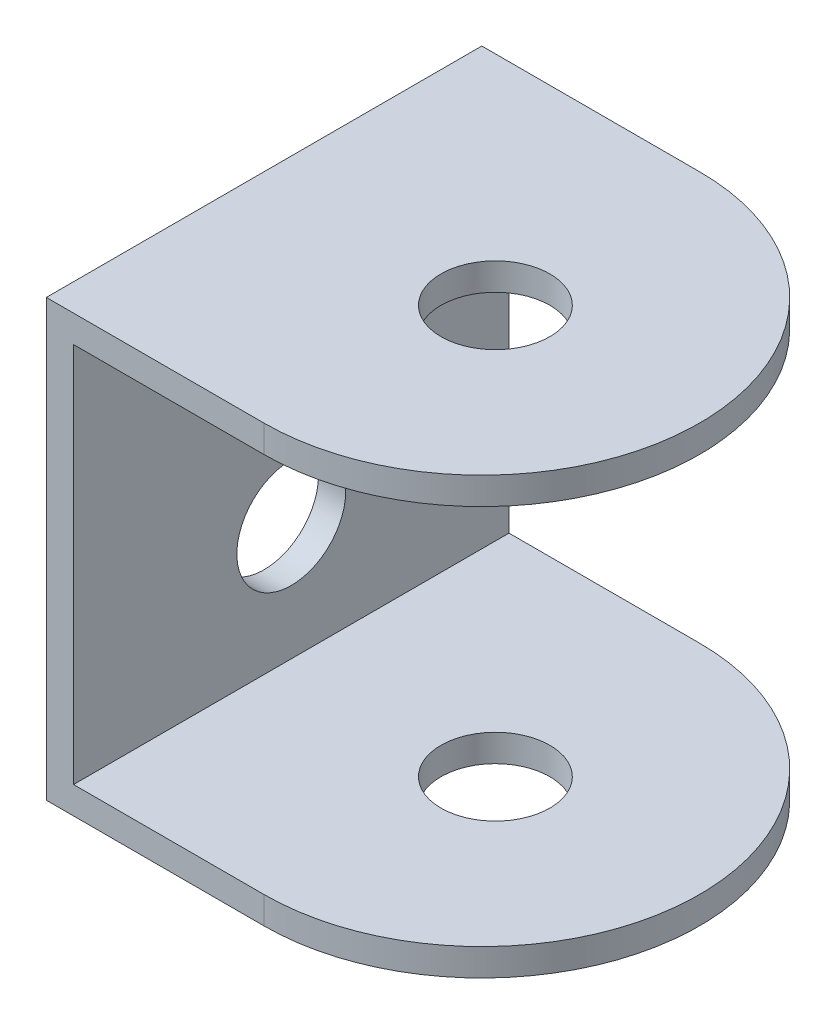
SolidWorks part; units mm, degrees
ref_plane "Front Plane" through (0, 0, 0) normal (0, 0, 1) x (1, 0, 0)
ref_plane "Top Plane" through (0, 0, 0) normal (0, 1, 0) x (1, 0, 0)
ref_plane "Right Plane" through (0, 0, 0) normal (1, 0, 0) x (0, 0, -1)
sketch "Sketch1" plane through (0, 0, 0) normal (0, 0, 1) x (1, 0, 0)
  line L1 (0, 0) -> (25.4, 0)
  line L2 (0, 0) -> (0, 25.4)
  dimension "D2" = 25.4
extrude "Extrude-Thin1" add sketch "Sketch1" along normal blind 25.4 thin thin type one direction reverse wall 1.5875
sketch "Sketch3" plane through (1.5875, 0, 0) normal (1, 0, 0) x (0, 0, -1)
  line L0 (-12.7, 25.4) -> (-12.7, 1.5875) construction
  line L1 (-25.4, 25.4) -> (0, 25.4) construction
  line L2 (-25.4, 1.5875) -> (0, 1.5875) construction
  circle A0 centre (-12.7, 16.9333) radius 3.175
  circle A1 centre (-12.7, 8.4667) radius 3.175
  dimension "D1" = 6.35
  dimension "D2" = 6.35
  dimension "D3" = 8.4667
  dimension "D4" = 8.4667
extrude "Cut-Extrude1" cut sketch "Sketch3" against normal through all
sketch "Sketch4" plane through (0, 1.5875, 0) normal (0, 1, 0) x (1, 0, 0)
  line L0 (25.4, -25.4) -> (25.4, 0) construction
  circle A0 centre (12.7, -12.7) radius 3.175
  dimension "D1" = 6.35
  dimension "D2" = 12.7
fillet "Fillet1" radius 12.7 2 edges at (25.4, 0.7937, 0) (25.4, 0.7937, 25.4)
sketch "Sketch5" plane through (0, 0, 0) normal (-1, 0, 0) x (0, 0, 1)
  line L1 (25.4, 25.4) -> (0, 25.4)
  line L2 (25.4, 25.4) -> (25.4, 23.8125)
  line L3 (25.4, 23.8125) -> (0, 23.8125)
  line L4 (0, 25.4) -> (0, 23.8125)
  dimension "D1" = 1.5875
extrude "Boss-Extrude1" add sketch "Sketch5" against normal blind 25.4
sketch "Sketch6" plane through (0, 25.4, 0) normal (0, 1, 0) x (1, 0, 0)
  line L0 (0, -25.4) -> (0, 0) construction
  line L2 (25.4, -25.4) -> (25.4, 0) construction
  line L3 (0, -25.4) -> (25.4, -25.4) construction
  line L4 (0, 0) -> (25.4, 0) construction
  circle A0 centre (13.4937, -12.7) radius 3.175
  circle A1 centre (12.7, -12.7) radius 12.7
  line M1 (25.4, 0) -> (0, 0)
  line M3 (0, -25.4) -> (25.4, -25.4)
  line M4 (25.4, -25.4) -> (25.4, 0)
  dimension "D1" = 6.35
  dimension "D2" = 13.4937
extrude "Cut-Extrude3" cut sketch "Sketch6" against normal blind 25.4 contours M4 M1 | A0 | M3 M4 region at (13.4937, 25.4, 12.7) region at (22.5632, 25.4, 22.5632) region at (22.5632, 25.4, 2.8368)
